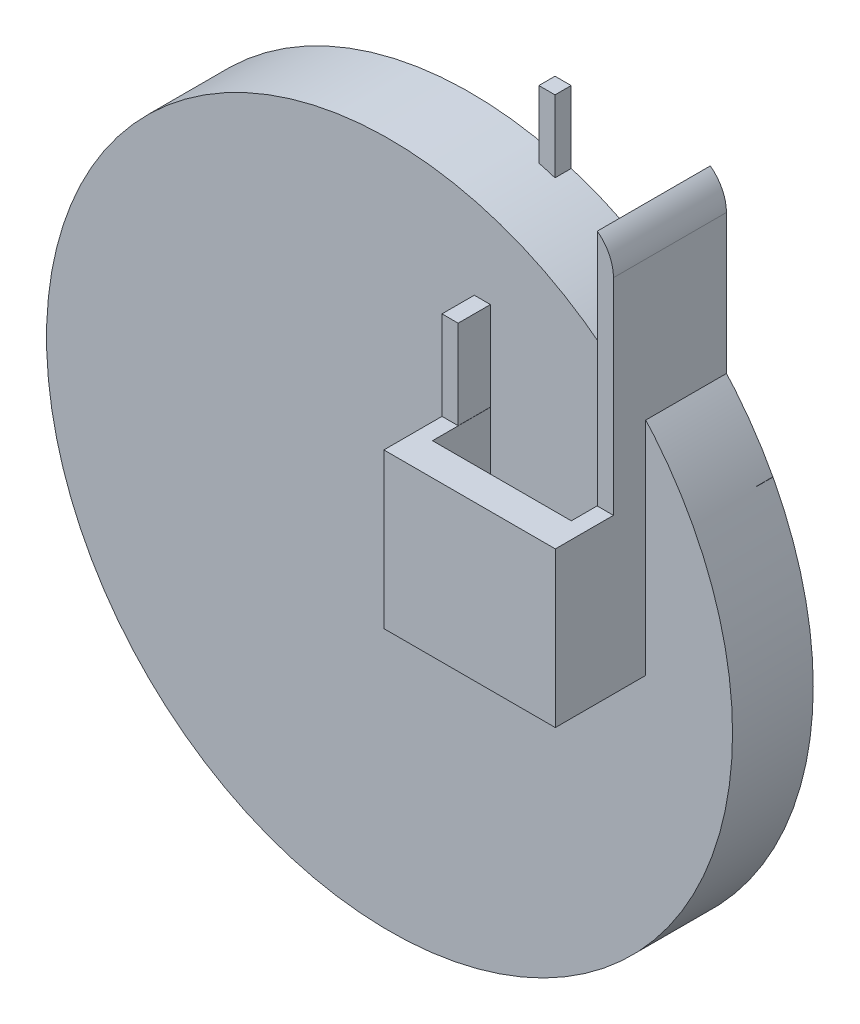
SolidWorks part; units mm, degrees
ref_plane "Front Plane" through (0, 0, 0) normal (0, 0, 1) x (1, 0, 0)
ref_plane "Top Plane" through (0, 0, 0) normal (0, 1, 0) x (1, 0, 0)
ref_plane "Right Plane" through (0, 0, 0) normal (1, 0, 0) x (0, 0, -1)
sketch "Plan" plane through (0, 0, 0) normal (0, 0, 1) x (1, 0, 0)
  line L0 (0, 0) -> (0, 60) construction
  line L1 (0, 0) -> (51.9615, -30) construction
  line L2 (0, 0) -> (-51.9615, -30) construction
  line L3 (0, 0) -> (0, 60) construction
  line L4 (0, 0) -> (51.9615, -30) construction
  line L5 (42.3527, 42.5) -> (-42.3527, 42.5) construction
  line L6 (-10, 60) -> (10, 60)
  line L7 (-10, 60) -> (-10, 25)
  line L8 (-10, 25) -> (10, 25)
  line L9 (10, 60) -> (10, 25)
  circle A0 centre (0, 0) radius 60
  text T0 "Tyre"
  point P13 (0, 60)
  point P17 (-10, 42.5)
  dimension "D1" = 3
  dimension "D5" = 120
  dimension "D2" = 120
  dimension "D3" = 35
  dimension "D4" = 20
sketch "Stepper Motor" plane through (0, 0, 0) normal (0, 0, 1) x (1, 0, 0)
  line L1 (10.7429, 49.5) -> (29.7429, 49.5)
  line L2 (10.7429, 49.5) -> (10.7429, 21.5)
  line L3 (10.7429, 21.5) -> (29.7429, 21.5)
  line L4 (29.7429, 49.5) -> (29.7429, 21.5)
  line L5 (10.7429, 47) -> (0.7429, 47)
  line L6 (10.7429, 47) -> (10.7429, 38)
  line L7 (10.7429, 38) -> (0.7429, 38)
  line L8 (0.7429, 47) -> (0.7429, 38)
  line L9 (-1.5598, 42.5) -> (29.7429, 42.5) construction
  line L11 (42.3527, 42.5) -> (-42.3527, 42.5) construction
  text T0 "Stepper"
  point P11 (0.7429, 42.5)
  dimension "D1" = 28
  dimension "D2" = 19
  dimension "D3" = 9
  dimension "D4" = 10
  dimension "D5" = 2.5
sketch "DC Motor" plane through (0, 0, 0) normal (0, 0, 1) x (1, 0, 0)
  line L0 (63.4697, 76.7537) -> (25.6249, 76.7537) construction
  line L1 (38.6689, 84.3037) -> (63.6689, 84.3037)
  line L2 (38.6689, 84.3037) -> (38.6689, 69.2037)
  line L3 (38.6689, 69.2037) -> (63.6689, 69.2037)
  line L4 (63.6689, 84.3037) -> (63.6689, 69.2037)
  line L5 (28.6689, 79.8287) -> (38.6689, 79.8287)
  line L6 (28.6689, 79.8287) -> (28.6689, 73.6787)
  line L7 (28.6689, 73.6787) -> (38.6689, 73.6787)
  line L8 (38.6689, 79.8287) -> (38.6689, 73.6787)
  text T0 "DC"
  point P10 (38.6689, 76.7537)
  point P11 (38.6689, 76.7537)
  dimension "D1" = 25
  dimension "D2" = 15.1
  dimension "D3" = 10
  dimension "D4" = 6.15
sketch "Sketch4" plane through (0, 0, 0) normal (0, 0, 1) x (1, 0, 0)
  circle A0 centre (0, 0) radius 42.5
  dimension "D1" = 85
extrude "base" add sketch "Sketch4" along normal blind 10
sketch "arm plan" plane through (0, 0, 0) normal (0, 0, 1) x (1, 0, 0)
  line L1 (12.5, 49.5) -> (29.7429, 49.5)
  line L2 (12.5, 49.5) -> (12.5, 0.8253)
  line L3 (12.5, 0.8253) -> (29.7429, 0.8253)
  line L4 (29.7429, 49.5) -> (29.7429, 0.8253)
  line L5 (10.5, 20) -> (31.7429, 20)
  line L6 (10.5, 20) -> (10.5, 0.8253)
  line L7 (10.5, 0.8253) -> (31.7429, 0.8253)
  line L8 (31.7429, 20) -> (31.7429, 0.8253)
  line L9 (4.9314, 20) -> (37.5, 20)
  line L10 (4.9314, 20) -> (4.9314, 0.8253)
  line L11 (4.9314, 0.8253) -> (37.5, 0.8253)
  line L12 (37.5, 20) -> (37.5, 0.8253)
  dimension "D1" = 17.2429
  dimension "D2" = 48.6747
  dimension "D3" = 19.1747
  dimension "D4" = 21.2429
  dimension "D5" = 2
  dimension "D6" = 5.5686
sketch "Sketch10" plane through (0, 0, 0) normal (0, 0, 1) x (1, 0, 0)
  line L1 (10.5, 20) -> (31.7429, 20)
  line L2 (10.5, 20) -> (10.5, 0.8253)
  line L3 (10.5, 0.8253) -> (31.7429, 0.8253)
  line L4 (31.7429, 20) -> (31.7429, 0.8253)
extrude "Boss-Extrude1" add sketch "Sketch10" along normal blind 21.2 separate body
sketch "Sketch11" plane through (0, 0, 0) normal (0, 0, 1) x (1, 0, 0)
  line L0 (10.7429, 49.5) -> (29.7429, 49.5) construction
  line L1 (4.9314, 0.8253) -> (37.5, 0.8253)
  line L2 (4.9314, 0.8253) -> (4.9314, 49.5)
  line L3 (4.9314, 49.5) -> (37.5, 49.5)
  line L4 (37.5, 0.8253) -> (37.5, 49.5)
  line L5 (37.5, 20) -> (37.5, 0.8253) construction
extrude "Boss-Extrude2" add sketch "Sketch11" along normal blind 2
ref_plane "Plane1" through (0, 20, 0) normal (0, 1, 0) x (1, 0, 0)
sketch "Sketch13" plane through (0, 20, 0) normal (0, 1, 0) x (1, 0, 0)
  line L0 (0, 0) -> (51.9615, 0) construction
  line L1 (12.5214, 0) -> (29.7214, 0)
  line L2 (12.5214, 0) -> (12.5214, -17.2)
  line L3 (12.5214, -17.2) -> (29.7214, -17.2)
  line L4 (29.7214, 0) -> (29.7214, -17.2)
  line L5 (21.1214, -21.2) -> (21.1214, 0) construction
  line L6 (31.7429, -21.2) -> (10.5, -21.2) construction
  point P10 (21.1214, -17.2)
  dimension "D1" = 17.2
  dimension "D2" = 17.2
extrude "Cut-Extrude2" cut sketch "Sketch13" against normal blind 15.2
ref_plane "Plane3" through (37.5, 0, 0) normal (1, 0, 0) x (0, 0, -1)
sketch "Sketch17" plane through (37.5, 0, 0) normal (1, 0, 0) x (0, 0, -1)
  line L0 (10.56, 20) -> (-10.56, 20) construction
  line L1 (-2, 49.5) -> (-14, 49.5)
  line L2 (-2, 49.5) -> (-2, 20)
  line L3 (-2, 20) -> (-14, 20)
  line L4 (-14, 49.5) -> (-14, 20)
  dimension "D1" = 12
extrude "Boss-Extrude4" add sketch "Sketch17" against normal up to surface (32.5686 mm away) up to face at (4.9314, 25.1627, 1)
sketch "Sketch12" plane through (0, 0, 0) normal (0, 0, 1) x (1, 0, 0)
  line L0 (29.7429, 49.5) -> (29.7429, 0.8253) construction
  line L1 (4.9314, 20) -> (10.5, 20)
  line L2 (4.9314, 20) -> (4.9314, 52.7578)
  line L3 (4.9314, 52.7578) -> (10.5, 52.7578)
  line L4 (10.5, 20) -> (10.5, 52.7578)
  line L5 (12.5, 52.7578) -> (29.7429, 52.7578)
  line L6 (12.5, 52.7578) -> (12.5, 20)
  line L7 (12.5, 20) -> (29.7429, 20)
  line L8 (29.7429, 52.7578) -> (29.7429, 20)
  line L9 (10.5, 20) -> (31.7429, 20) construction
  line L10 (10.5, 20) -> (10.5, 0.8253) construction
  line L11 (37.5, 20) -> (31.7429, 20)
  line L12 (37.5, 20) -> (37.5, 52.7578)
  line L13 (37.5, 52.7578) -> (31.7429, 52.7578)
  line L14 (31.7429, 20) -> (31.7429, 52.7578)
  line L15 (31.7429, 20) -> (31.7429, 0.8253) construction
extrude "Cut-Extrude3" cut sketch "Sketch12" along normal up to surface (14 mm away) up to face at (21.1686, 27.375, 14)
sketch "Sketch18" plane through (37.5, 0, 0) normal (1, 0, 0) x (0, 0, -1)
  line L0 (-24.7048, 10.8253) -> (7.5077, 10.8253) construction
  line L1 (-21.2, 0.8253) -> (-2, 0.8253) construction
  line L2 (0, 60) -> (0, -60) construction
  line L3 (-6, 10.8253) -> (-9, 10.8253)
  line L4 (-6, 10.8253) -> (-6, 27.2794)
  line L5 (-6, 27.2794) -> (-9, 27.2794)
  line L6 (-9, 10.8253) -> (-9, 27.2794)
  dimension "D1" = 10
  dimension "D2" = 3
  dimension "D3" = 6
  dimension "D4" = 16.4541
extrude "Cut-Extrude4" cut sketch "Sketch18" against normal up to surface (27 mm away) up to face at (10.5, 22.5813, 9.3)
fillet "Fillet1" radius 5 1 edges at (31.7429, 49.5, 7)
fillet "Fillet2" radius 1 8 edges at (30.7429, 27.2794, 6) (11.5, 27.2794, 9) (11.5, 27.2794, 6) (11.5107, 10.8253, 6) (11.5107, 10.8253, 9) (30.7429, 27.2794, 9) (30.7321, 10.8253, 9) (30.7321, 10.8253, 6)
sketch "Sketch19" plane through (0, 0, 0) normal (0, 0, 1) x (1, 0, 0)
  line L0 (4.9314, 0.8253) -> (37.5, 0.8253) construction
  line L1 (10.5, 20) -> (4.9314, 20) construction
  line L2 (21.1214, 25.3936) -> (21.1214, 5.3751) construction
  line L5 (10.5, 0.8253) -> (31.7429, 0.8253) construction
  circle A0 centre (7.7157, 16) radius 1.5
  circle A1 centre (7.7157, 4.8253) radius 1.5
  circle A2 centre (34.5272, 4.8253) radius 1.5
  circle A3 centre (34.5272, 16) radius 1.5
  point P8 (7.7157, 20)
  point P15 (21.1214, 0.8253)
  dimension "D1" = 4
  dimension "D2" = 4
extrude "Cut-Extrude5" cut sketch "Sketch19" along normal blind 10
ref_plane "Plane4" through (10.5, 0, 0) normal (-1, 0, 0) x (0, 0, 1)
sketch "Sketch21" plane through (10.5, 0, 0) normal (-1, 0, 0) x (0, 0, 1)
  line L0 (0, 20) -> (0, 49.5) construction
  line L1 (14, 49.5) -> (2, 49.5)
  line L2 (14, 49.5) -> (14, 31)
  line L3 (14, 31) -> (2, 31)
  line L4 (2, 49.5) -> (2, 31)
  dimension "D1" = 2
  dimension "D2" = 18.5
extrude "Cut-Extrude6" cut sketch "Sketch21" against normal up to surface (2 mm away) up to face at (12.5, 28.6532, 7.3)
